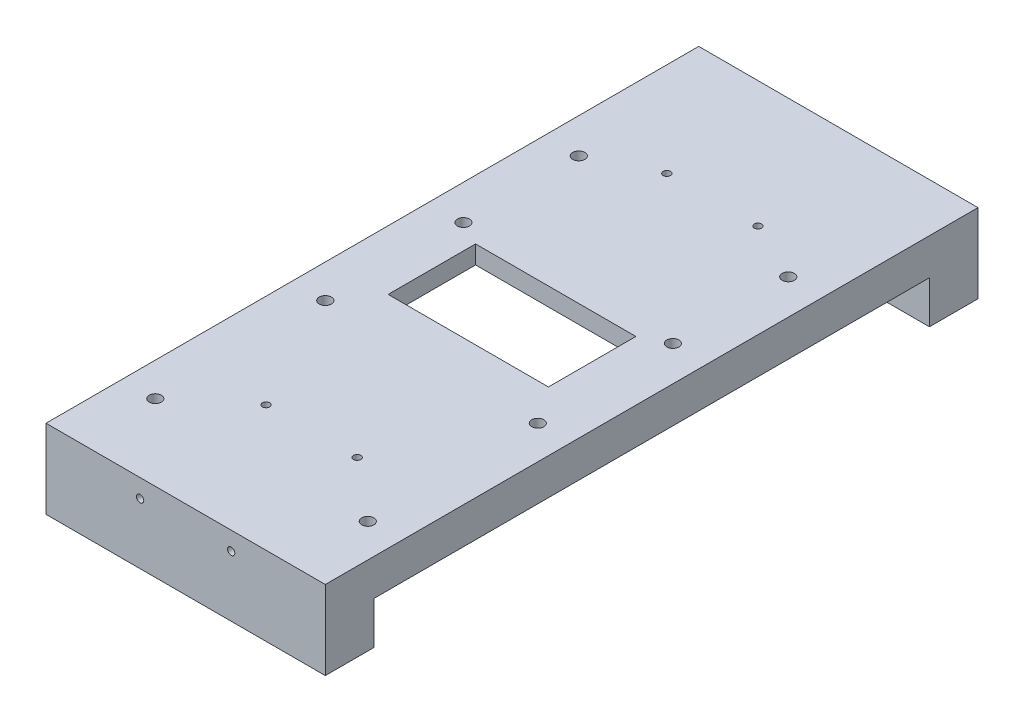
SolidWorks part; units mm, degrees
other "标注1"
sketch "草图3" plane through (-22.25, 4, -10) normal (-0.231, 0.6469, -0.7268) x (-0.9696, -0.2151, 0.1167)
ref_plane "前视基准面" through (0, 0, 0) normal (0, 0, 1) x (1, 0, 0)
ref_plane "上视基准面" through (0, 0, 0) normal (0, 1, 0) x (1, 0, 0)
ref_plane "右视基准面" through (0, 0, 0) normal (1, 0, 0) x (0, 0, -1)
other "Configuration Table"
sketch "草图4" plane through (0, 0, 0) normal (0, 1, 0) x (1, 0, 0)
  line L1 (-23, -53.75) -> (23, -53.75)
  line L2 (-23, -53.75) -> (-23, 53.75)
  line L3 (-23, 53.75) -> (23, 53.75)
  line L4 (23, -53.75) -> (23, 53.75)
  line L5 (-23, -53.75) -> (23, 53.75) construction
  line L6 (-23, 53.75) -> (23, -53.75) construction
  point P0 (0, 0)
  dimension "D1" = 107.5
  dimension "D2" = 46
extrude "凸台-拉伸1" add sketch "草图4" along normal blind 3
sketch "草图5" plane through (0, 0, 0) normal (0, -1, 0) x (1, 0, 0)
  line L0 (-11.75, 28) -> (11.75, -28) construction
  line L1 (-11.75, 28) -> (11.75, 28)
  line L2 (-11.75, 28) -> (-11.75, -28)
  line L3 (-11.75, -28) -> (11.75, -28)
  line L4 (11.75, 28) -> (11.75, -28)
  dimension "D1" = 56
  dimension "D2" = 23.5
extrude "凸台-拉伸2" add sketch "草图5" along normal blind 12.4
sketch "草图6" plane through (-11.75, 0, 0) normal (-1, 0, 0) x (0, 0, 1)
  line L0 (28, -12.4) -> (-28, -12.4) construction
  line L1 (-25, -12.4) -> (25, -12.4)
  circle A0 centre (0, -12.4) radius 1.75
  circle A1 centre (0, -12.4) radius 3
  circle A2 centre (25, -12.4) radius 0.75
  circle A3 centre (25, -12.4) radius 1.5
  circle A4 centre (-25, -12.4) radius 0.75
  circle A5 centre (-25, -12.4) radius 1.5
  dimension "D1" = 3.5
  dimension "D2" = 6
  dimension "D3" = 1.5
  dimension "D4" = 3
  dimension "D5" = 50
extrude "切除-拉伸1" cut sketch "草图6" against normal through all contours A4 | A0 | A2
extrude "切除-拉伸2" cut sketch "草图6<3>" against normal blind 2.7 contours A1
sketch "草图6<3>" plane through (-11.75, 0, 0) normal (-1, 0, 0) x (0, 0, 1) same geometry as "草图6"
extrude "切除-拉伸3" cut sketch "草图6<4>" along normal blind 2.7 from surface contours A1 starting at face at (11.75, -9.595, 0)
sketch "草图6<4>" plane through (-11.75, 0, 0) normal (-1, 0, 0) x (0, 0, 1) same geometry as "草图6"
extrude "切除-拉伸4" cut sketch "草图6<5>" against normal blind 1.2 contours A3 | A5
sketch "草图6<5>" plane through (-11.75, 0, 0) normal (-1, 0, 0) x (0, 0, 1) same geometry as "草图6"
extrude "切除-拉伸5" cut sketch "草图6<6>" along normal blind 1.2 from surface contours A3 | A5 starting at face at (11.75, -9.47, 0)
sketch "草图6<6>" plane through (-11.75, 0, 0) normal (-1, 0, 0) x (0, 0, 1) same geometry as "草图6"
sketch "草图7" plane through (0, -12.4, 0) normal (0, -1, 0) x (-1, 0, 0)
  line L0 (9.2499, -6) -> (9.2499, 6) construction
  line L1 (-9.2499, -20) -> (-9.2499, 20) construction
  line L2 (9.2499, 0) -> (-9.2499, 0) construction
  circle A0 centre (9.2499, -20) radius 0.7
  circle A1 centre (-9.2499, -20) radius 0.7
  circle A2 centre (-9.2499, -6) radius 0.7
  circle A3 centre (9.2499, -6) radius 0.7
  circle A4 centre (9.2499, 6) radius 0.7
  circle A5 centre (-9.2499, 6) radius 0.7
  circle A6 centre (-9.2499, 20) radius 0.7
  circle A7 centre (9.2499, 20) radius 0.7
  dimension "D1" = 1.4
  dimension "D2" = 18.4999
  dimension "D3" = 12
  dimension "D4" = 40
extrude "切除-拉伸6" cut sketch "草图7" against normal blind 2
sketch "草图8" plane through (0, -12.4, 0) normal (0, -1, 0) x (1, 0, 0)
  line L1 (-8.2, 7.2) -> (8.2, 7.2)
  line L2 (-8.2, 7.2) -> (-8.2, -7.2)
  line L3 (-8.2, -7.2) -> (8.2, -7.2)
  line L4 (8.2, 7.2) -> (8.2, -7.2)
  line L8 (-8.2, 7.2) -> (-11.75, 7.2) construction
  line L9 (-11.75, -3) -> (-11.75, -23.5) construction
  line L10 (11.75, 7.2) -> (8.2, 7.2) construction
  line L11 (11.75, -23.5) -> (11.75, -3) construction
  line L12 (8.2, 28) -> (8.2, 7.2) construction
  line L13 (11.75, 28) -> (-11.75, 28) construction
  line L14 (8.2, -28) -> (8.2, -7.2) construction
  line L15 (-11.75, -28) -> (11.75, -28) construction
  dimension "D1" = 14.4
  dimension "D2" = 16.4
extrude "切除-拉伸7" cut sketch "草图8" against normal through all from offset 2 offset against normal yes
sketch "草图9" plane through (0, 0, 0) normal (0, -1, 0) x (1, 0, 0)
  line L0 (-23, 53.75) -> (23, 53.75) construction
  line L1 (-23, 53.75) -> (23, 53.75)
  line L2 (-23, 53.75) -> (-23, 45.75)
  line L3 (-23, 45.75) -> (23, 45.75)
  line L4 (23, 53.75) -> (23, 45.75)
  line L5 (23, 53.75) -> (23, -53.75) construction
  line L6 (23, -53.75) -> (-23, -53.75) construction
  line L7 (-23, -53.75) -> (23, -53.75)
  line L8 (-23, -53.75) -> (-23, -45.75)
  line L9 (-23, -45.75) -> (23, -45.75)
  line L10 (23, -53.75) -> (23, -45.75)
  line L11 (-23, -53.75) -> (-23, 53.75) construction
  line L12 (-23, 41.9103) -> (-20, 41.9103) construction
  line L13 (-20, 45.75) -> (-23, 45.75)
  line L14 (-20, 45.75) -> (-20, -45.75)
  line L15 (-20, -45.75) -> (-23, -45.75)
  line L16 (-23, 45.75) -> (-23, -45.75)
  line L17 (23, -45.75) -> (20, -45.75)
  line L18 (23, -45.75) -> (23, 45.75)
  line L19 (23, 45.75) -> (20, 45.75)
  line L20 (20, -45.75) -> (20, 45.75)
  line L22 (20, 41.9103) -> (23, 41.9103) construction
  line M17 (23, -53.75) -> (23, 53.75)
  line M18 (23, 53.75) -> (-23, 53.75)
  line M19 (-23, 53.75) -> (-23, -53.75)
  line M20 (-23, -53.75) -> (23, -53.75)
  dimension "D1" = 8
  dimension "D2" = 3
extrude "凸台-拉伸3" add sketch "草图9" along normal blind 10 contours L3 M19 M17 M18 | L9 M19 M20 M17 region at (0, 0, 49.75) region at (0, 0, -49.75)
extrude "凸台-拉伸4" add sketch "草图9<3>" along normal blind 3 contours L14 L3 L9 M19 | L20 L9 L3 M17 region at (-21.5, 0, 0) region at (21.5, 0, 0)
sketch "草图9<3>" plane through (0, 0, 0) normal (0, -1, 0) x (1, 0, 0) same geometry as "草图9"
sketch "草图10" plane through (0, 0, 53.75) normal (0, 0, 1) x (1, 0, 0)
  line L1 (-7.5, 0) -> (7.5, 0) construction
  circle A0 centre (-7.5, 0) radius 0.6
  circle A1 centre (7.5, 0) radius 0.6
  dimension "D2" = 1.2
  dimension "D1" = 15
extrude "切除-拉伸8" cut sketch "草图10" against normal blind 2
sketch "草图11" plane through (0, 3, 0) normal (0, 1, 0) x (1, 0, 0)
  line L0 (-8.2, 7.2) -> (8.2, 7.2) construction
  line L1 (-13.2, 7.2) -> (13.2, 7.2)
  line L2 (-13.2, 7.2) -> (-13.2, -7.2)
  line L3 (-13.2, -7.2) -> (13.2, -7.2)
  line L4 (13.2, 7.2) -> (13.2, -7.2)
  line L5 (8.2, -7.2) -> (-8.2, -7.2) construction
  line L6 (-13.2, 0) -> (13.2, 0) construction
  line L7 (-8.2, -7.2) -> (-8.2, 7.2) construction
  dimension "D1" = 5
extrude "切除-拉伸9" cut sketch "草图11" against normal blind 5
sketch "草图12" plane through (0, -2, 0) normal (0, 1, 0) x (1, 0, 0)
  line L0 (-9.975, 0) -> (9.975, 0) construction
  line L1 (-11.75, 0) -> (-8.2, 0) construction
  line L2 (-11.75, 7.2) -> (-11.75, -7.2) construction
  line L3 (-8.2, -7.2) -> (-8.2, 7.2) construction
  circle A0 centre (-9.975, 0) radius 0.5
  circle A1 centre (9.975, 0) radius 0.5
  dimension "D1" = 1
extrude "切除-拉伸10" cut sketch "草图12" against normal blind 2
sketch "草图13" plane through (0, -12.4, 0) normal (0, -1, 0) x (1, 0, 0)
  line L0 (-8.75, 2.6) -> (-6.75, 2.6)
  line L1 (-6.75, 2.6) -> (-6.75, 5.75)
  line L2 (-6.75, 5.75) -> (-3.55, 5.75)
  line L3 (-3.55, 5.75) -> (-3.55, -5.75)
  line L4 (-3.55, -5.75) -> (-6.75, -5.75)
  line L5 (-6.75, -5.75) -> (-6.75, -2.6)
  line L6 (-6.75, -2.6) -> (-8.75, -2.6)
  line L7 (-8.75, -2.6) -> (-8.75, 2.6)
  line L8 (-11.75, 23.5) -> (-11.75, 3) construction
  line L9 (-9.05, 0) -> (-8.75, 0) construction
  line L10 (-9.05, 1.75) -> (-9.05, -1.75) construction
  dimension "D1" = 3
  dimension "D2" = 5.2
  dimension "D3" = 11.5
  dimension "D4" = 2
  dimension "D5" = 3.2
extrude "切除-拉伸11" cut sketch "草图13" against normal through all
sketch "草图15" plane through (0, 0, 0) normal (0, -1, 0) x (1, 0, 0)
  line L1 (-11.75, 31.5) -> (11.75, 31.5) construction
  line L2 (-11.75, 31.5) -> (-11.75, 34.5) construction
  line L3 (-11.75, 34.5) -> (11.75, 34.5) construction
  line L4 (11.75, 31.5) -> (11.75, 34.5) construction
  line L5 (0, 33) -> (0, -33) construction
  line L6 (11.75, 3) -> (11.75, 23.5) construction
  line L8 (-11.75, -31.5) -> (11.75, -31.5) construction
  line L9 (-11.75, -31.5) -> (-11.75, -34.5) construction
  line L10 (-11.75, -34.5) -> (11.75, -34.5) construction
  line L11 (11.75, -31.5) -> (11.75, -34.5) construction
  line L12 (11.75, -23.5) -> (11.75, -3) construction
  line L13 (-11.75, 33) -> (-7.5, 33) construction
  line L14 (-7.5, 33) -> (7.5, 33) construction
  line L15 (7.5, 33) -> (11.75, 33) construction
  line L16 (-11.75, -33) -> (-7.5, -33) construction
  line L17 (-7.5, -33) -> (7.5, -33) construction
  line L18 (7.5, -33) -> (11.75, -33) construction
  line L19 (-11.75, -3) -> (-11.75, -23.5) construction
  circle A0 centre (-7.5, 33) radius 0.6
  circle A1 centre (7.5, 33) radius 0.6
  circle A2 centre (-7.5, -33) radius 0.6
  circle A3 centre (7.5, -33) radius 0.6
  dimension "D2" = 1.2
  dimension "D1" = 3
  dimension "D3" = 15
  dimension "D4" = 33
extrude "切除-拉伸13" cut sketch "草图15" against normal through all
sketch "草图14" plane through (0, 0, -28) normal (0, 0, -1) x (-1, 0, 0)
  line L0 (11.75, 0) -> (-11.75, 0) construction
  line L1 (-11.75, 0) -> (11.75, 0)
  line L2 (-11.75, 0) -> (-11.75, -12.4)
  line L3 (-11.75, -12.4) -> (11.75, -12.4)
  line L4 (11.75, 0) -> (11.75, -12.4)
  line L5 (11.75, -12.4) -> (-11.75, -12.4) construction
  line L6 (-11.75, -12.4) -> (-11.75, 0) construction
  line L7 (11.75, -12.4) -> (11.75, 0) construction
extrude "切除-拉伸12" cut sketch "草图14" against normal up to surface (56 mm away) up to face at (0, -6.2, 28)
sketch "草图16" plane through (0, 0, 0) normal (0, -1, 0) x (-1, 0, 0)
  line L0 (23, 9.25) -> (17.25, 9.25) construction
  line L1 (23, 53.75) -> (23, -53.75) construction
  line L2 (-17.25, 9.25) -> (-23, 9.25) construction
  line L3 (-23, -53.75) -> (-23, 53.75) construction
  line L4 (23, -53.75) -> (-23, -53.75) construction
  circle A0 centre (17.25, 9.25) radius 1
  circle A1 centre (17.25, 28.25) radius 1
  circle A2 centre (-17.25, 28.25) radius 1
  circle A3 centre (-17.25, 9.25) radius 1
  circle A4 centre (-17.25, 28.25) radius 1.5
  circle A5 centre (-17.25, 9.25) radius 1.5
  circle A6 centre (17.25, 9.25) radius 1.5
  circle A7 centre (17.25, 28.25) radius 1.5
  dimension "D4" = 2
  dimension "D5" = 3
  dimension "D1" = 5.75
  dimension "D2" = 63
  dimension "D3" = 19
extrude "切除-拉伸14" cut sketch "草图16" against normal through all contours A0 | A1 | A2 | A3
extrude "切除-拉伸15" cut sketch "草图16<3>" against normal blind 1
sketch "草图16<3>" plane through (0, 0, 0) normal (0, -1, 0) x (-1, 0, 0) same geometry as "草图16"
sketch "草图17" plane through (0, 0, 0) normal (0, -1, 0) x (1, 0, 0)
  line L0 (23, 53.75) -> (23, -53.75) construction
  line L1 (-23, 53.75) -> (23, 53.75) construction
  line L2 (17.5, 41.25) -> (23, 41.25) construction
  line L3 (-17.5, 41.25) -> (-23, 41.25) construction
  line L4 (-23, -53.75) -> (-23, 53.75) construction
  circle A0 centre (17.5, 41.25) radius 1
  circle A1 centre (17.5, 13.25) radius 1
  circle A2 centre (-17.5, 13.25) radius 1
  circle A3 centre (-17.5, 41.25) radius 1
  dimension "D1" = 2
  dimension "D2" = 5.5
  dimension "D3" = 12.5
  dimension "D4" = 28
extrude "切除-拉伸16" cut sketch "草图17" against normal through all
sketch "草图18" plane through (0, 0, 0) normal (0, -1, 0) x (1, 0, 0)
  circle A0 centre (-17.5, 13.25) radius 1.5
  circle A1 centre (17.5, 13.25) radius 1.5
  circle A2 centre (17.5, 41.25) radius 1.5
  circle A3 centre (-17.5, 41.25) radius 1.5
  circle A4 centre (-17.5, 41.25) radius 1 construction
  circle A5 centre (-17.5, 13.25) radius 1 construction
  circle A6 centre (17.5, 13.25) radius 1 construction
  circle A7 centre (17.5, 41.25) radius 1 construction
  dimension "D1" = 3
extrude "切除-拉伸17" cut sketch "草图18" against normal blind 1
